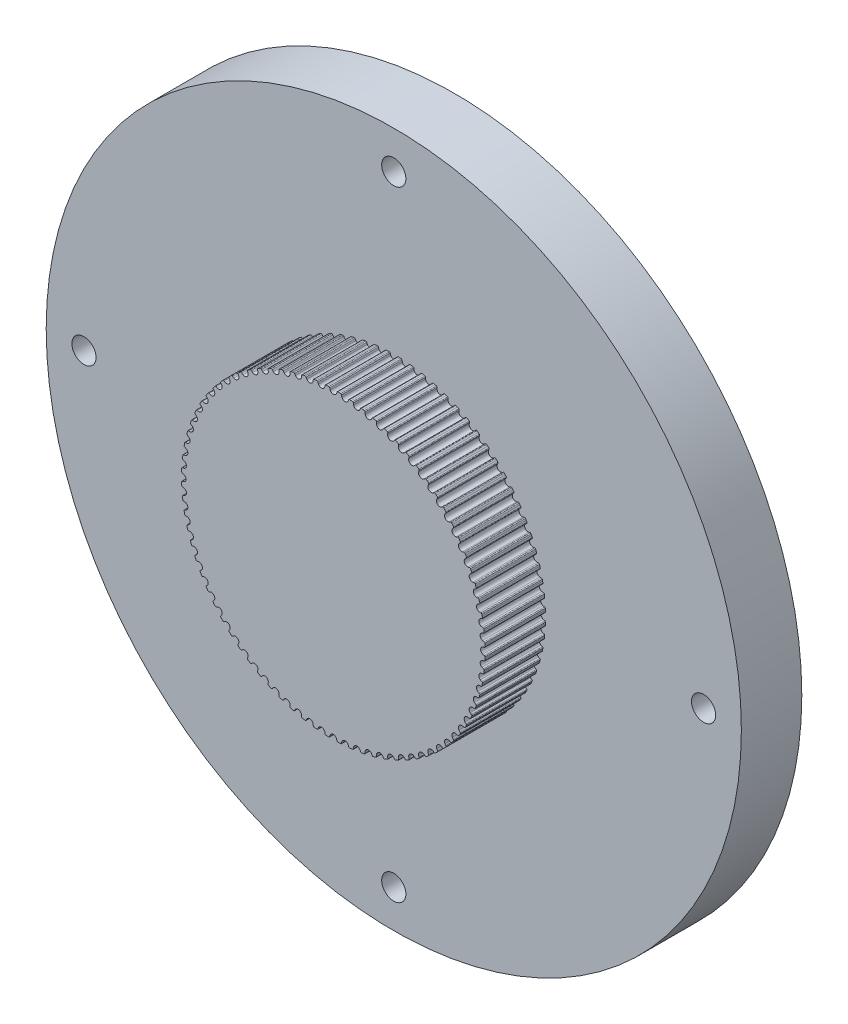
SolidWorks part; units mm, degrees
ref_plane "Front Plane" through (0, 0, 0) normal (1, 0, 0) x (0, 1, 0)
ref_plane "Top Plane" through (0, 0, 0) normal (0, 0, 1) x (0, 1, 0)
ref_plane "Right Plane" through (0, 0, 0) normal (0, 1, 0) x (-1, 0, 0)
sketch "Sketch1" plane through (0, 0, 0) normal (0, 0, 1) x (0, 1, 0)
  line L0 (45, 0) -> (57.5, 0) construction
  circle A0 centre (0, 0) radius 57.5
  circle A1 centre (0, 0) radius 45 construction
  circle A2 centre (51.25, 0) radius 2
  circle A3 centre (0, -51.25) radius 2
  circle A4 centre (-51.25, 0) radius 2
  circle A5 centre (0, 51.25) radius 2
  dimension "D1" = 115
  dimension "D2" = 90
  dimension "D3" = 4
  dimension "D4" = 4
extrude "Boss-Extrude1" add sketch "Sketch1" along normal blind 10
sketch "Sketch2" plane through (0, 0, 10) normal (0, 0, 1) x (1, 0, 0)
  circle A0 centre (0, 0) radius 25.4648
  dimension "D1" = 50.9296
extrude "Boss-Extrude2" add sketch "Sketch2" along normal blind 10
sketch "Sketch3" plane through (0, 0, 20) normal (0, 0, 1) x (1, 0, 0)
  line L0 (-0.7443, 25.0978) -> (-1, 25.0889)
  line L1 (0, 24.3689) -> (0, 25.1088) construction
  line L2 (0.7443, 25.0978) -> (1, 25.0889)
  line L3 (-1, 25.0889) -> (-1.0142, 25.4446)
  line L4 (1.0124, 25.4447) -> (1, 25.0889)
  circle A0 centre (0, 0) radius 25.1088 construction
  circle A1 centre (0, 0) radius 25.4648 construction
  arc A2 (-0.7443, 25.0978) -> (-0.5905, 24.9684) centre (-0.7391, 24.9478) cw
  arc A3 (-0.5905, 24.9684) -> (-0.5185, 24.7103) centre (0.4, 25.1056) ccw
  arc A4 (-0.5185, 24.7103) -> (0.5185, 24.7103) centre (0, 24.9335) ccw
  arc A5 (0.5905, 24.9684) -> (0.5185, 24.7103) centre (-0.4, 25.1056) cw
  arc A6 (0.7443, 25.0978) -> (0.5905, 24.9684) centre (0.7391, 24.9478) ccw
  arc A7 (-1.0142, 25.4446) -> (1.0124, 25.4447) centre (0, 0) cw
  circle A8 centre (0, 0) radius 25.4648 construction
  dimension "D1" = 0.356
  dimension "D2" = 1
  dimension "D3" = 0.15
  dimension "D4" = 0.4
  dimension "D6" = 0.5645
  dimension "D5" = 2
extrude "Cut-Extrude1" cut sketch "Sketch3" against normal up to surface (10 mm away) up to face at (25.4648, 0, 10)
pattern_circular "CirPattern1" count 80 over 360 about axis through (0, 0, 20) along (0, 0, -1) of "Cut-Extrude1"
equation "\"teeth count\" = 80"
equation "\"pulley pitch\"= 2mm"
equation "\"D1@Sketch2\"=\"pulley pitch\"*\"teeth count\"/pi"
equation "\"D1@CirPattern1\"=\"teeth count\""
